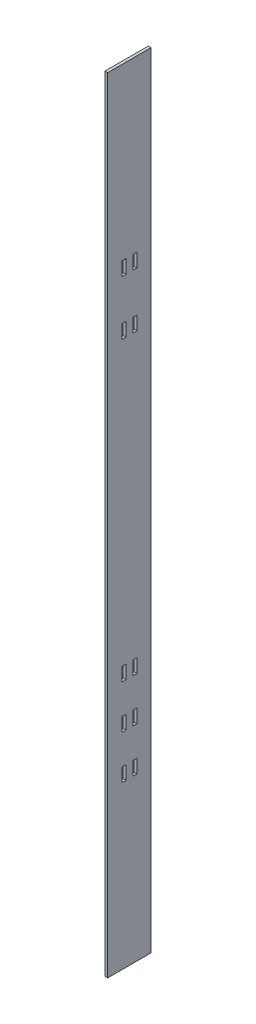
SolidWorks part; units mm, degrees
ref_plane "Front Plane" through (0, 0, 0) normal (0, 0, 1) x (1, 0, 0)
ref_plane "Top Plane" through (0, 0, 0) normal (0, 1, 0) x (1, 0, 0)
ref_plane "Right Plane" through (0, 0, 0) normal (1, 0, 0) x (0, 0, -1)
sketch "Sketch1" plane through (0, 0, 0) normal (1, 0, 0) x (0, 0, -1)
  line L1 (-25.4, 457.2) -> (25.4, 457.2)
  line L2 (-25.4, 457.2) -> (-25.4, -457.2)
  line L3 (-25.4, -457.2) -> (25.4, -457.2)
  line L4 (25.4, 457.2) -> (25.4, -457.2)
  line L5 (-25.4, 457.2) -> (25.4, -457.2) construction
  line L6 (-25.4, -457.2) -> (25.4, 457.2) construction
  point P0 (0, 0)
  dimension "D1" = 914.4
  dimension "D2" = 50.8
extrude "Boss-Extrude1" add sketch "Sketch1" along normal blind 3.175
sketch "Sketch2" plane through (3.175, 0, 0) normal (1, 0, 0) x (0, 0, -1)
  line L0 (-25.4, -457.2) -> (25.4, -457.2) construction
  line L1 (4, -201.6125) -> (8.7625, -201.6125)
  line L2 (4, -201.6125) -> (4, -217.4875)
  line L3 (4, -217.4875) -> (8.7625, -217.4875)
  line L4 (8.7625, -201.6125) -> (8.7625, -217.4875)
  line L5 (4, -201.6125) -> (8.7625, -217.4875) construction
  line L6 (4, -217.4875) -> (8.7625, -201.6125) construction
  point P0 (6.3813, -209.55)
  dimension "D1" = 4.7625
  dimension "D2" = 15.875
  dimension "D3" = 239.7125
  dimension "D4" = 4
extrude "Cut-Extrude1" cut sketch "Sketch2" against normal through all
mirror "Mirror1" about plane through (0, 0, 0) normal (0, 0, 1) of "Cut-Extrude1"
pattern_linear "LPattern1" count 2 spacing 50.8 along (0, 1, 0) count 2 spacing 50.8 along (0, -1, 0) of "Mirror1"
sketch "Sketch3" plane through (3.175, 0, 0) normal (1, 0, 0) x (0, 0, -1)
  line L0 (8.7625, -166.6875) -> (8.7625, -150.8125) construction
  line L1 (4, 195.2625) -> (8.7625, 195.2625)
  line L2 (4, 195.2625) -> (4, 179.3875)
  line L3 (4, 179.3875) -> (8.7625, 179.3875)
  line L4 (8.7625, 195.2625) -> (8.7625, 179.3875)
  line L5 (4, 195.2625) -> (8.7625, 179.3875) construction
  line L6 (4, 179.3875) -> (8.7625, 195.2625) construction
  line L7 (8.7625, -150.8125) -> (4, -150.8125) construction
  line L8 (4, -150.8125) -> (4, -166.6875) construction
  line L9 (0, 0) -> (0, 52.1648) construction
  line L10 (-4, 179.3875) -> (-8.7625, 195.2625) construction
  line L11 (-4, 195.2625) -> (-8.7625, 179.3875) construction
  line L12 (-8.7625, 195.2625) -> (-8.7625, 179.3875)
  line L13 (-4, 179.3875) -> (-8.7625, 179.3875)
  line L14 (-4, 195.2625) -> (-4, 179.3875)
  line L15 (-4, 195.2625) -> (-8.7625, 195.2625)
  point P0 (6.3812, 187.325)
  point P18 (-6.3812, 187.325)
  dimension "D1" = 330.2
extrude "Cut-Extrude2" cut sketch "Sketch3" against normal through all
pattern_linear "LPattern2" count 2 spacing 63.5 along (0, 1, 0) of "Cut-Extrude2"
